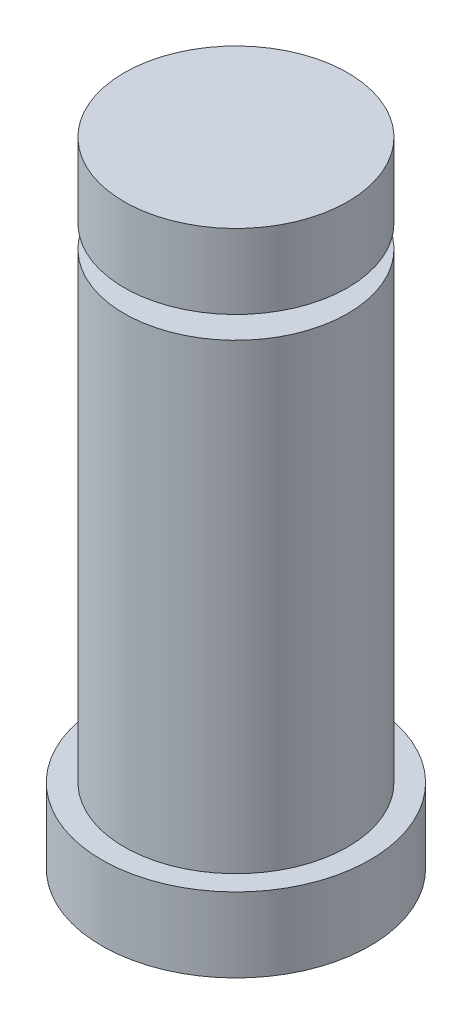
SolidWorks part; units mm, degrees
material "K110"
ref_plane "Front Plane" through (0, 0, 0) normal (0, 0, 1) x (1, 0, 0)
ref_plane "Top Plane" through (0, 0, 0) normal (0, 1, 0) x (1, 0, 0)
ref_plane "Right Plane" through (0, 0, 0) normal (1, 0, 0) x (0, 0, -1)
sketch "Sketch1" plane through (0, 0, 0) normal (0, 0, 1) x (1, 0, 0)
  line L0 (0, 0) -> (9, 0)
  line L1 (9, 0) -> (9, 5)
  line L2 (9, 5) -> (7.5, 5)
  line L3 (7.5, 5) -> (7.5, 42.5)
  line L4 (7.5, 42.5) -> (0, 42.5)
  line L5 (0, 42.5) -> (0, 0)
  line L6 (0, 47.5) -> (0, -5) construction
  point P9 (8.25, 5)
  dimension "D1" = 5
  dimension "D2" = 5
  dimension "D3" = 18
  dimension "D4" = 15
  dimension "D5" = 5
  dimension "D6" = 37.5
revolve "Revolve1" add sketch "Sketch1" angle 360 about L6
sketch "Sketch2" plane through (0, 0, 0) normal (0, 0, 1) x (1, 0, 0)
  line L0 (7.5, 5) -> (7.5, 42.5) construction
  line L1 (7.5, 36) -> (4.85, 36)
  line L2 (7.5, 36) -> (7.5, 37.5)
  line L3 (7.5, 37.5) -> (4.85, 37.5)
  line L4 (4.85, 36) -> (4.85, 37.5)
  line L5 (0, 42.5) -> (0, 5) construction
  line L6 (7.5, 42.5) -> (-7.5, 42.5) construction
  line L7 (9, 5) -> (-9, 5) construction
  dimension "D1" = 1.5
  dimension "D2" = 2.65
  dimension "D3" = 31
revolve "Cut-Revolve1" cut sketch "Sketch2" angle 360 about L5
